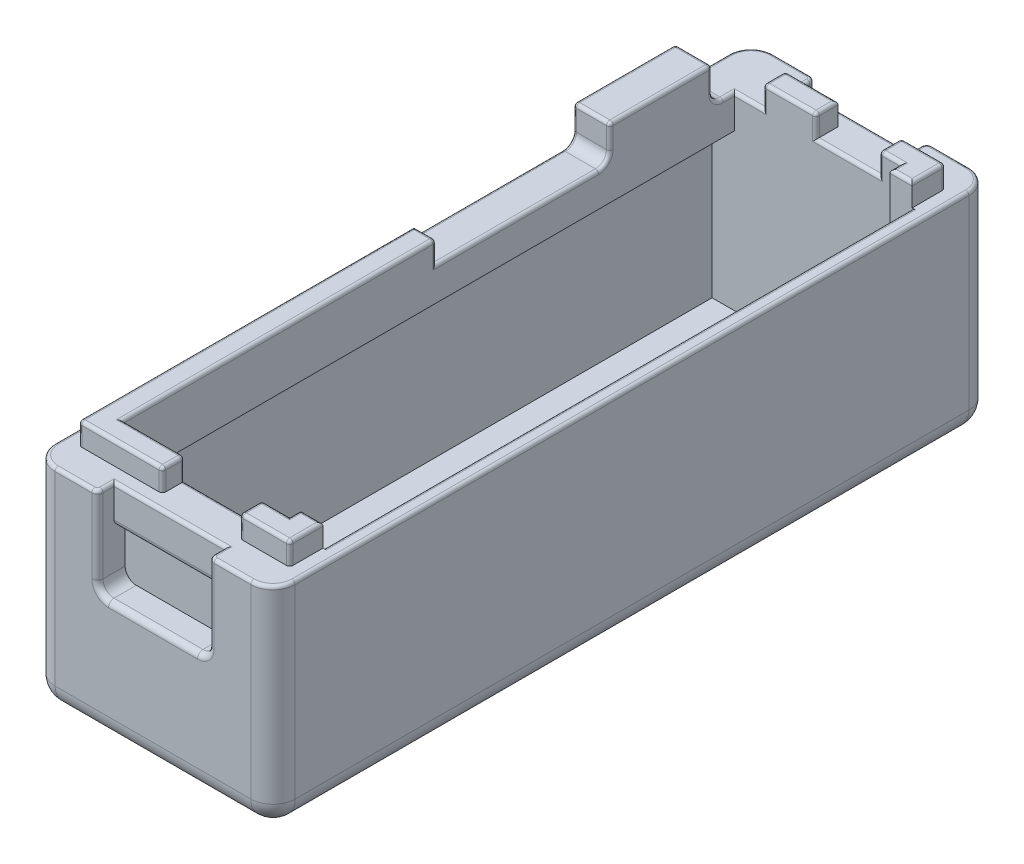
SolidWorks part; units mm, degrees
ref_plane "Front Plane" through (0, 0, 0) normal (0, 0, 1) x (1, 0, 0)
ref_plane "Top Plane" through (0, 0, 0) normal (0, 1, 0) x (1, 0, 0)
ref_plane "Right Plane" through (0, 0, 0) normal (1, 0, 0) x (0, 0, -1)
sketch "Sketch1" plane through (0, 0, 0) normal (0, 1, 0) x (1, 0, 0)
  line L0 (-5, 32.3) -> (-5, 30.8)
  line L1 (-10.8, 32.3) -> (-5, 32.3)
  line L2 (-10.8, 32.3) -> (-10.8, -32.3)
  line L3 (-10.8, -32.3) -> (-5, -32.3)
  line L4 (10.8, 32.3) -> (10.8, -32.3)
  line L5 (-10.8, 32.3) -> (10.8, -32.3) construction
  line L6 (-10.8, -32.3) -> (10.8, 32.3) construction
  line L7 (-5, 30.8) -> (5, 30.8)
  line L8 (5, 30.8) -> (5, 32.3)
  line L9 (-5, -32.3) -> (-5, -30.8)
  line L10 (-5, -30.8) -> (5, -30.8)
  line L11 (5, -30.8) -> (5, -32.3)
  line L12 (-9.5, 29.5) -> (-9.5, -29.5)
  line L14 (9.5, 29.5) -> (9.5, -29.5)
  line L18 (-6.3, -29.5) -> (6.3, -29.5)
  line L20 (-6.3, -32.3) -> (-6.3, -29.5) construction
  line L22 (-9.5, -31) -> (9.5, -31) construction
  line L23 (6.3, -29.5) -> (6.3, -32.3) construction
  line L24 (-6.3, 29.5) -> (6.3, 29.5)
  line L26 (-5, 31) -> (5, 31)
  line L27 (-9.5, 31) -> (9.5, 31) construction
  line L29 (6.3, 29.5) -> (6.3, 32.3) construction
  line L30 (-6.3, 32.3) -> (-6.3, 29.5) construction
  line L31 (5, -32.3) -> (10.8, -32.3)
  line L32 (-10.8, -32.3) -> (10.8, -32.3) construction
  line L33 (5, 32.3) -> (10.8, 32.3)
  line L34 (-10.8, 32.3) -> (10.8, 32.3) construction
  line L35 (-6.3, 29.5) -> (-9.5, 29.5)
  line L36 (6.3, 29.5) -> (9.5, 29.5)
  line L37 (6.3, -29.5) -> (9.5, -29.5)
  line L38 (-6.3, -29.5) -> (-9.5, -29.5)
  line L39 (-9.5, 31) -> (-9.5, -31) construction
  line L40 (9.5, 31) -> (9.5, -31) construction
  point P0 (0, 0)
  dimension "D1" = 64.6
  dimension "D2" = 21.6
  dimension "D3" = 5.8
  dimension "D4" = 5.8
  dimension "D5" = 1.5
  dimension "D6" = 5.8
  dimension "D7" = 5.8
  dimension "D8" = 1.5
extrude "Boss-Extrude1" add sketch "Sketch1" along normal blind 17 contours L33 L8 L7 L0 L1 L2 L3 L9 L10 L11 L31 L4 L14 L18 L12 L24 region at (-5.6812, 0, -31.65)
sketch "Sketch2" plane through (0, 0, 0) normal (0, -1, 0) x (1, 0, 0)
  line L1 (-10.8, 32.3) -> (10.8, 32.3)
  line L2 (-10.8, 32.3) -> (-10.8, -32.3)
  line L3 (-10.8, -32.3) -> (10.8, -32.3)
  line L4 (10.8, 32.3) -> (10.8, -32.3)
extrude "Boss-Extrude2" add sketch "Sketch2" along normal blind 2
sketch "Sketch3" plane through (0, 17, 0) normal (0, 1, 0) x (1, 0, 0)
  line L1 (-9.5, 29.5) -> (9.5, 29.5)
  line L2 (-9.5, 29.5) -> (-9.5, -29.5)
  line L3 (-9.5, -29.5) -> (9.5, -29.5)
  line L4 (9.5, 29.5) -> (9.5, -29.5)
  line L5 (-7.5, 27.5) -> (7.5, 27.5)
  line L6 (-7.5, 27.5) -> (-7.5, -27.5)
  line L7 (-7.5, -27.5) -> (7.5, -27.5)
  line L8 (7.5, 27.5) -> (7.5, -27.5)
  dimension "D1" = 2
  dimension "D2" = 2
  dimension "D3" = 2
  dimension "D4" = 2
extrude "Boss-Extrude3" add sketch "Sketch3" along normal blind 2 and the other way blind 3
sketch "Sketch4" plane through (0, 19, 0) normal (0, 1, 0) x (1, 0, 0)
  line L0 (9.5, 29.5) -> (-9.5, 29.5) construction
  line L1 (6.8997, 26.5) -> (15.3477, 26.5)
  line L2 (6.8997, 26.5) -> (6.8997, -26.5)
  line L3 (6.8997, -26.5) -> (15.3477, -26.5)
  line L4 (15.3477, 26.5) -> (15.3477, -26.5)
  line L5 (-9.5, -29.5) -> (9.5, -29.5) construction
  line L6 (5.5387, 34.5636) -> (5.5387, 26.5)
  line L7 (-12.9492, 0.6845) -> (-4.9077, 0.6845)
  line L8 (-12.9492, 0.6845) -> (-12.9492, 30.4987)
  line L9 (-12.9492, 30.4987) -> (-4.9077, 30.4987)
  line L10 (-4.9077, 0.6845) -> (-4.9077, 30.4987)
  line L13 (5.5387, 34.5636) -> (-0.1556, 34.5636)
  line L14 (-0.1556, 26.5) -> (-0.1556, 34.5636)
  line L15 (-1.9491, -24.502) -> (5, -24.502)
  line L16 (-1.9491, -24.502) -> (-1.9491, -32.3)
  line L17 (-1.9491, -32.3) -> (5, -32.3)
  line L18 (5, -24.502) -> (5, -32.3)
  line L19 (5.5387, 26.5) -> (-0.1556, 26.5)
  dimension "D1" = 3
  dimension "D2" = 3
extrude "Cut-Extrude1" cut sketch "Sketch4" against normal up to surface (2 mm away) up to face at (0, 17, 0)
fillet "Fillet1" radius 2 8 edges at (0, -2, 32.3) (-10.8, -2, 0) (0, -2, -32.3) (10.8, -2, 0) (10.8, 7.5, -32.3) (-10.8, 7.5, -32.3) (-10.8, 7.5, 32.3) (10.8, 7.5, 32.3)
sketch "Sketch5" plane through (0, 0, -32.3) normal (0, 0, -1) x (-1, 0, 0)
  line L0 (-8.8, 0) -> (-5, 0) construction
  line L1 (-6.2539, 0) -> (7.1427, 0)
  line L2 (-6.2539, 0) -> (-6.2539, 9)
  line L3 (-6.2539, 9) -> (7.1427, 9)
  line L4 (7.1427, 0) -> (7.1427, 9)
  dimension "D1" = 9
extrude "Boss-Extrude4" add sketch "Sketch5" against normal up to surface (1.5 mm away) up to face at (0, 8.5, -30.8)
sketch "Sketch6" plane through (0, 0, 32.3) normal (0, 0, 1) x (1, 0, 0)
  line L0 (-8.8, 0) -> (-5, 0) construction
  line L1 (-6.9, 0) -> (7.1273, 0)
  line L2 (-6.9, 0) -> (-6.9, 9)
  line L3 (-6.9, 9) -> (7.1273, 9)
  line L4 (7.1273, 0) -> (7.1273, 9)
  dimension "D1" = 9
extrude "Boss-Extrude5" add sketch "Sketch6" against normal up to surface (1.5 mm away) up to face at (0, 8.5, 30.8)
sketch "Sketch7" plane through (-10.8, 0, 0) normal (-1, 0, 0) x (0, 0, 1)
  line L0 (-32.3, 0) -> (-32.3, 17) construction
  line L2 (-30.3, 17) -> (30.3, 17) construction
  line L3 (-25.5, 17) -> (-16.3, 17)
  line L4 (-25.5, 17) -> (-25.5, 20.16)
  line L5 (-25.5, 20.16) -> (-16.3, 20.16)
  line L6 (-16.3, 17) -> (-16.3, 20.16)
  dimension "D1" = 6.8
  dimension "D2" = 3.16
  dimension "D3" = 9.2
extrude "Boss-Extrude6" add sketch "Sketch7" against normal up to surface (3.3 mm away) up to face at (-7.5, 16.6667, -0.2282)
sketch "Sketch10" plane through (0, 17, 0) normal (0, 1, 0) x (1, 0, 0)
  line L1 (-10.4728, 30.8) -> (10.4526, 30.8)
  line L2 (-10.4728, 30.8) -> (-10.4728, 27.5)
  line L3 (-10.4728, 27.5) -> (10.4526, 27.5)
  line L4 (10.4526, 30.8) -> (10.4526, 27.5)
  line L5 (-10.3073, -27.5) -> (10.4526, -27.5)
  line L6 (-10.3073, -27.5) -> (-10.3073, -30.8)
  line L7 (-10.3073, -30.8) -> (10.4526, -30.8)
  line L8 (10.4526, -27.5) -> (10.4526, -30.8)
extrude "Boss-Extrude7" add sketch "Sketch10" against normal up to surface (17 mm away) up to face at (0, 0, 0)
sketch "Sketch8" plane through (0, 0, -30.8) normal (0, 0, -1) x (-1, 0, 0)
  line L0 (-5, 17) -> (-5, 9) construction
  line L1 (-5, 13.6) -> (5, 13.6)
  line L2 (-5, 13.6) -> (-5, 9)
  line L3 (-5, 9) -> (5, 9)
  line L4 (5, 13.6) -> (5, 9)
  line L5 (5, 17) -> (5, 9) construction
  line L6 (-5, 9) -> (5, 9) construction
  line L7 (5, 9) -> (-5, 9) construction
  dimension "D1" = 4.6
  dimension "D2" = 0
extrude "Cut-Extrude2" cut sketch "Sketch8" against normal blind 1
sketch "Sketch9" plane through (0, 0, 30.8) normal (0, 0, 1) x (1, 0, 0)
  line L0 (5, 17) -> (5, 9) construction
  line L1 (-5, 9) -> (5, 9)
  line L2 (-5, 9) -> (-5, 13.6)
  line L3 (-5, 13.6) -> (5, 13.6)
  line L4 (5, 9) -> (5, 13.6)
  dimension "D1" = 4.6
extrude "Cut-Extrude3" cut sketch "Sketch9" against normal blind 1
fillet "Fillet2" radius 0.5 2 edges at (0, 13.6, -30.8) (0, 13.6, 30.8)
fillet "Fillet3" radius 1 4 edges at (-5, 9, -31.05) (5, 9, -31.05) (5, 9, 31.05) (-5, 9, 31.05)
fillet "Fillet4" radius 0.5 10 edges at (-5, 13.5, 32.3) (-4.7071, 9.2929, 32.3) (0, 9, 32.3) (4.7071, 9.2929, 32.3) (5, 13.5, -32.3) (4.7071, 9.2929, -32.3) (0, 9, -32.3) (-4.7071, 9.2929, -32.3) (5, 13.5, 32.3) (-5, 13.5, -32.3)
fillet "Fillet7" radius 1 2 edges at (-9.15, 17, -25.5) (-9.15, 17, -16.3)
fillet "Fillet5" radius 0.3 26 edges at (-5, 17, -31.3) (-5.1464, 17, -32.1536) (-7.15, 17, -32.3) (-10.2142, 17, -31.7142) (-10.8, 17, 7.5) (-10.2142, 17, 31.7142) (-7.15, 17, 32.3) (-5.1464, 17, 32.1536) (5, 17, -31.3) (5.1464, 17, -32.1536) (7.15, 17, -32.3) (10.2142, 17, -31.7142) (5, 17, 31.3) (5.1464, 17, 32.1536) (7.15, 17, 32.3) (10.2142, 17, 31.7142) (0, 17, -30.8) (-10.8, 17, -28.4) (-10.8, 19.08, -16.3) (-10.8, 20.16, -20.9) (-10.8, 19.08, -25.5) (-5, 17, 31.3) (0, 17, 30.8) (10.8, 17, 0) (-10.8, 17.2929, -25.7929) (-10.8, 17.2929, -16.0071)
sketch "Sketch11" plane through (0, 17, 0) normal (0, 1, 0) x (1, 0, 0)
  line L0 (7.5, 26.5) -> (7.5, -26.5) construction
  line L1 (7.5, 26.5) -> (9.5, 26.5)
  line L2 (7.5, 26.5) -> (7.5, -26.5)
  line L3 (7.5, -26.5) -> (9.5, -26.5)
  line L4 (9.5, 26.5) -> (9.5, -26.5)
  line L5 (7.5, 26.5) -> (7.5, 27.5) construction
extrude "Cut-Extrude4" cut sketch "Sketch11" against normal blind 5
fillet "Fillet6" radius 0.3 50 edges at (-10.7121, 20.0721, -16.3879) (-10.7121, 20.0721, -25.4121) (-9, 20.16, -16.3) (-9, 20.16, -25.5) (-7.5, 17, -27) (-6.2039, 17, -27.5) (-4.9077, 18, -27.5) (-4.9077, 18, -29.5) (-4.9077, 19, -28.5) (-2.5317, 19, -29.5) (-0.1556, 19, -28.5) (-2.5317, 19, -27.5) (-0.1556, 18, -27.5) (5.5387, 18, -27.5) (2.6916, 17, -27.5) (5.5387, 18, -29.5) (5.5387, 19, -28.5) (6.5194, 19, -27.5) (7.5, 19, -27) (8.5, 19, -26.5) (9.5, 18, -29.5) (7.5194, 19, -29.5) (9.5, 19, -28) (9.5, 17, 0) (9.5, 19, 28) (9.5, 18, 29.5) (7.25, 19, 29.5) (8.5, 19, 26.5) (7.5, 19, 27) (6.25, 19, 27.5) (5, 18, 27.5) (5, 19, 28.5) (5, 18, 29.5) (-1.9491, 18, 29.5) (-1.9491, 18, 27.5) (1.5255, 17, 27.5) (-7.5, 18, -0.6845) (-7.5, 17, -7.9923) (-7.5, 19.08, -16.3) (-7.5, 20.16, -20.9) (-7.5, 19.08, -25.5) (-8.5, 19, -0.6845) (-4.7245, 19, 27.5) (-7.5, 19, 13.4077) (-1.9491, 19, 28.5) (-5.7245, 19, 29.5) (-9.5, 19, 14.4077) (-9.5, 18, 29.5) (-7.5, 17.2929, -16.0071) (-7.5, 17.2929, -25.7929)
